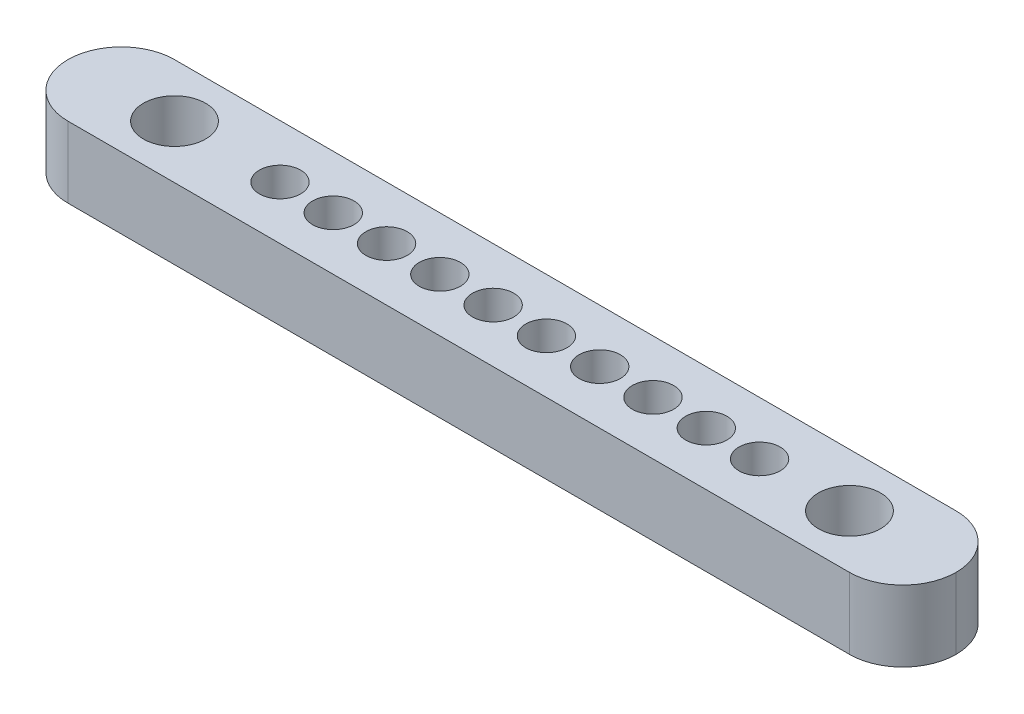
SolidWorks part; units mm, degrees
ref_plane "Front Plane" through (0, 0, 0) normal (0, 0, 1) x (1, 0, 0)
ref_plane "Top Plane" through (0, 0, 0) normal (0, 1, 0) x (1, 0, 0)
ref_plane "Right Plane" through (0, 0, 0) normal (1, 0, 0) x (0, 0, -1)
sketch "草圖1" plane through (0, 0, 0) normal (0, 1, 0) x (1, 0, 0)
  line L1 (25, -3) -> (-25, -3)
  line L2 (25, -3) -> (25, 3)
  line L3 (25, 3) -> (-25, 3)
  line L4 (-25, -3) -> (-25, 3)
  line L5 (25, -3) -> (-25, 3) construction
  line L6 (25, 3) -> (-25, -3) construction
  circle A0 centre (-19, 0) radius 1.75
  circle A1 centre (19, 0) radius 1.75
  circle A2 centre (-13.062, 0) radius 1.1628
  circle A3 centre (-10.062, 0) radius 1.1628
  circle A4 centre (-7.062, 0) radius 1.1628
  circle A5 centre (-4.062, 0) radius 1.1628
  circle A6 centre (-1.062, 0) radius 1.1628
  circle A7 centre (1.938, 0) radius 1.1628
  circle A8 centre (4.938, 0) radius 1.1628
  circle A9 centre (7.938, 0) radius 1.1628
  circle A10 centre (10.938, 0) radius 1.1628
  circle A11 centre (13.938, 0) radius 1.1628
  point P0 (0, 0)
  dimension "D5" = 3.5
  dimension "D1" = 50
  dimension "D2" = 6
  dimension "D3" = 38
  dimension "D4" = 19
  dimension "D6" = 10
extrude "填料-伸長1" add sketch "草圖1" along normal blind 4
fillet "圓角1" radius 3 4 edges at (25, 2, 3) (25, 2, -3) (-25, 2, -3) (-25, 2, 3)
